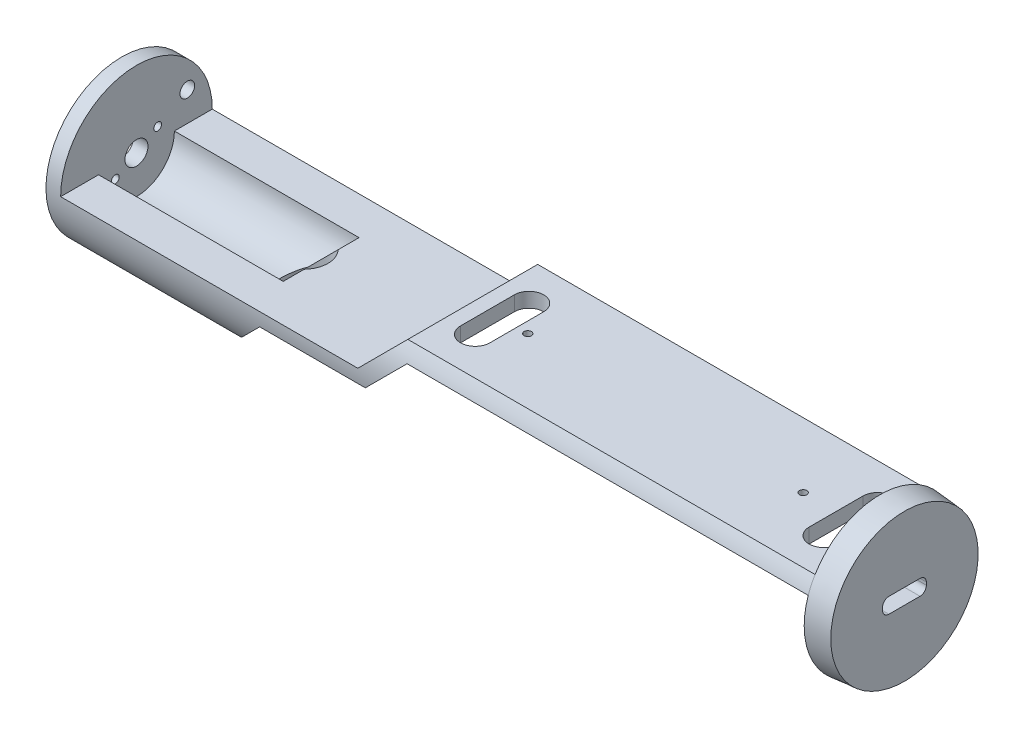
SolidWorks part; units mm, degrees
ref_plane "Front Plane" through (0, 0, 0) normal (0, 0, 1) x (1, 0, 0)
ref_plane "Top Plane" through (0, 0, 0) normal (0, 1, 0) x (1, 0, 0)
ref_plane "Right Plane" through (0, 0, 0) normal (1, 0, 0) x (0, 0, -1)
sketch "Sketch2" plane through (0, 0, 0) normal (1, 0, 0) x (0, 0, -1)
  circle A0 centre (0, 0) radius 15.5
  dimension "D1" = 31
extrude "Boss-Extrude1" add sketch "Sketch2" along normal blind 160
sketch "Sketch6" plane through (0, 0, 0) normal (0, 0, 1) x (1, 0, 0)
  line L0 (3, 15.5) -> (3, 0)
  line L1 (160, 15.5) -> (0, 15.5) construction
  line L2 (3, 0) -> (63.75, 0)
  line L4 (3, 15.5) -> (83, 15.5)
  line L5 (0, 15.5) -> (0, -15.5) construction
  line L7 (63.75, 0) -> (71.75, 8)
  line L8 (71.75, 8) -> (155, 8)
  line L10 (155, 8) -> (155, 15.5)
  line L11 (155, 15.5) -> (83, 15.5)
  line L12 (160, -15.5) -> (160, 15.5) construction
  dimension "D1" = 3
  dimension "D2" = 5
  dimension "D3" = 8
  dimension "D4" = 45
  dimension "D5" = 60.75
extrude "Cut-Extrude1" cut sketch "Sketch6" against normal through all both and the other way through all
sketch "Sketch7" plane through (0, 0, 0) normal (1, 0, 0) x (0, 0, -1)
  circle A0 centre (0, 0) radius 7.75
  dimension "D1" = 15.5
extrude "Cut-Extrude2" cut sketch "Sketch7" along normal blind 30 from surface contours A0 starting at face at (3, 7.75, 0)
chamfer "Chamfer1" distance 7.75 angle 45 1 edges at (33, 0, 0)
sketch "Sketch8" plane through (0, 0, 0) normal (0, 0, 1) x (1, 0, 0)
  line L0 (0, -10.75) -> (35.6458, -10.75)
  line L1 (0, 15.5) -> (0, -15.5) construction
  line L2 (35.6458, -10.75) -> (43.3958, -3)
  line L3 (43.3958, -3) -> (64.9926, -3)
  line L4 (3, 0) -> (63.75, 0) construction
  line L5 (3, -7.75) -> (33, -7.75) construction
  line L6 (160, -15.5) -> (160, 15.5) construction
  line L7 (155, 8) -> (71.75, 8) construction
  line L9 (0, -15.5) -> (160, -15.5) construction
  line L10 (155, -15.5) -> (0, -15.5)
  line L11 (0, -15.5) -> (0, -10.75)
  line L12 (64.9926, -3) -> (72.9926, 5)
  line L13 (72.9926, 5) -> (155, 5)
  line L15 (155, 5) -> (155, -15.5)
  line L17 (63.75, 0) -> (71.75, 8) construction
  dimension "D1" = 45
  dimension "D2" = 3
  dimension "D3" = 3
  dimension "D4" = 4
  dimension "D5" = 3
  dimension "D6" = 3
  dimension "D8" = 5
extrude "Cut-Extrude3" cut sketch "Sketch8" against normal through all both and the other way through all
sketch "Sketch9" plane through (0, 0, 0) normal (1, 0, 0) x (0, 0, -1)
  line L0 (8.9523, 5.1686) -> (-8.9523, -5.1686) construction
  line L1 (13.0769, 0) -> (-13.0769, 0) construction
  line L2 (-4.7371, 8.2049) -> (4.7371, -8.2049) construction
  circle A0 centre (4.3301, 2.5) radius 0.8
  circle A1 centre (-4.3301, -2.5) radius 0.8
  circle A2 centre (4.3301, 2.5) radius 1.25
  circle A3 centre (-4.3301, -2.5) radius 1.25
  circle A4 centre (0, 0) radius 2.35
  circle A5 centre (0, 0) radius 5 construction
  point P4 (0, 0)
  point P7 (0, 0)
  point P14 (0, 0)
  point P15 (0, 0)
  dimension "D3" = 1.6
  dimension "D4" = 2.5
  dimension "D2" = 10
  dimension "D5" = 4.7
  dimension "D1" = 30
extrude "Cut-Extrude4" cut sketch "Sketch9" along normal blind 10 contours A1 | A0 | A4 region at (0, 2.5, -4.3301) region at (0, -2.5, 4.3301) region at (0, 0, 0)
extrude "Cut-Extrude5" cut sketch "Sketch9<3>" along normal blind 1 contours A2 A0 | A3 A1 region at (0, 2.5, -3.1155) region at (0, -2.5, 5.5448)
sketch "Sketch9<3>" plane through (0, 0, 0) normal (1, 0, 0) x (0, 0, -1) same geometry as "Sketch9"
sketch "Sketch11" plane through (0, 0, 0) normal (1, 0, 0) x (0, 0, -1)
  line L0 (0, 0) -> (0, 22.0661) construction
  line L5 (-3.175, 1.58) -> (3.175, 1.58)
  line L6 (-4.475, 0.28) -> (-4.475, -0.28)
  line L7 (-3.175, -1.58) -> (3.175, -1.58)
  line L8 (4.475, 0.28) -> (4.475, -0.28)
  line L9 (-4.475, 1.58) -> (4.475, -1.58) construction
  line L10 (-4.475, -1.58) -> (4.475, 1.58) construction
  arc A2 (-4.475, -0.28) -> (-3.175, -1.58) centre (-3.175, -0.28) ccw
  arc A3 (3.175, -1.58) -> (4.475, -0.28) centre (3.175, -0.28) ccw
  arc A4 (3.175, 1.58) -> (4.475, 0.28) centre (3.175, 0.28) cw
  arc A5 (-3.175, 1.58) -> (-4.475, 0.28) centre (-3.175, 0.28) ccw
  point P3 (0, 0)
  dimension "D2" = 3.16
  dimension "D4" = 1.3
  dimension "D1" = 8.95
extrude "Cut-Extrude6" cut sketch "Sketch11" along normal blind 10 from surface starting at face at (155, 11.75, 0)
sketch "Sketch12" plane through (0, 0, 0) normal (0, 0, 1) x (1, 0, 0)
  line L2 (160, -15.5) -> (160, 15.5) construction
  line L3 (160, -15.5) -> (160, 15.5) construction
  line L5 (160, 15.5) -> (155, 15.5)
  line L6 (0, 0) -> (177.1073, 0) construction
  line L8 (155, 15.5) -> (160, 15.0626)
  line L9 (160, 15.0626) -> (160, 15.5)
  dimension "D1" = 5
revolve "Cut-Revolve1" cut sketch "Sketch12" angle 360 about L6
sketch "Sketch13" plane through (0, 0, 0) normal (1, 0, 0) x (0, 0, -1)
  line L0 (13.0348, 7.5256) -> (-13.0348, -7.5256) construction
  line L1 (9.9747, 0) -> (-9.9747, 0) construction
  circle A0 centre (10.3923, 6) radius 1.5
  circle A1 centre (-10.3923, -6) radius 1.5
  circle A2 centre (0, 0) radius 12 construction
  point P5 (0, 0)
  point P9 (0, 0)
  dimension "D2" = 3
  dimension "D3" = 24
  dimension "D1" = 30
extrude "Cut-Extrude7" cut sketch "Sketch13" along normal blind 10
cosmetic thread "Cosmetic Thread1" parameters "D1"=3, "D2"=4
cosmetic thread "Cosmetic Thread2" parameters "D1"=8, "D2"=4
sketch "Sketch14" plane through (0, 0, 0) normal (0, 1, 0) x (1, 0, 0)
  line L0 (0, 0) -> (183.562, 0) construction
  line L1 (72.9926, 14.6714) -> (72.9926, -14.6714) construction
  circle A0 centre (82.9926, 0) radius 0.75
  circle A1 centre (139.2926, 0) radius 0.75
  dimension "D1" = 1.5
  dimension "D2" = 56.3
  dimension "D3" = 10
extrude "Cut-Extrude8" cut sketch "Sketch14" along normal through all
sketch "Sketch16" plane through (0, 0, 0) normal (0, 1, 0) x (1, 0, 0)
  circle A0 centre (37.14, 0) radius 5
  dimension "D2" = 10
  dimension "D1" = 37.14
extrude "Cut-Extrude9" cut sketch "Sketch16" against normal blind 16
sketch "Sketch19" plane through (0, 0, 0) normal (0, 1, 0) x (1, 0, 0)
  line L0 (77.75, 5.5) -> (77.75, -5.5) construction
  line L1 (80.75, 5.5) -> (80.75, -5.5)
  line L2 (74.75, 5.5) -> (74.75, -5.5)
  line L3 (149, 5.5) -> (149, -5.5) construction
  line L4 (152, 5.5) -> (152, -5.5)
  line L5 (146, 5.5) -> (146, -5.5)
  line L6 (71.75, 13.2759) -> (71.75, -13.2759) construction
  line L7 (155, 13.2759) -> (155, -13.2759) construction
  arc A0 (80.75, 5.5) -> (74.75, 5.5) centre (77.75, 5.5) ccw
  arc A1 (74.75, -5.5) -> (80.75, -5.5) centre (77.75, -5.5) ccw
  arc A2 (152, 5.5) -> (146, 5.5) centre (149, 5.5) ccw
  arc A3 (146, -5.5) -> (152, -5.5) centre (149, -5.5) ccw
  point P2 (77.75, 0)
  point P7 (149, 0)
  dimension "D3" = 3
  dimension "D1" = 6
  dimension "D2" = 6
  dimension "D4" = 11
extrude "Cut-Extrude12" cut sketch "Sketch19" along normal blind 16
